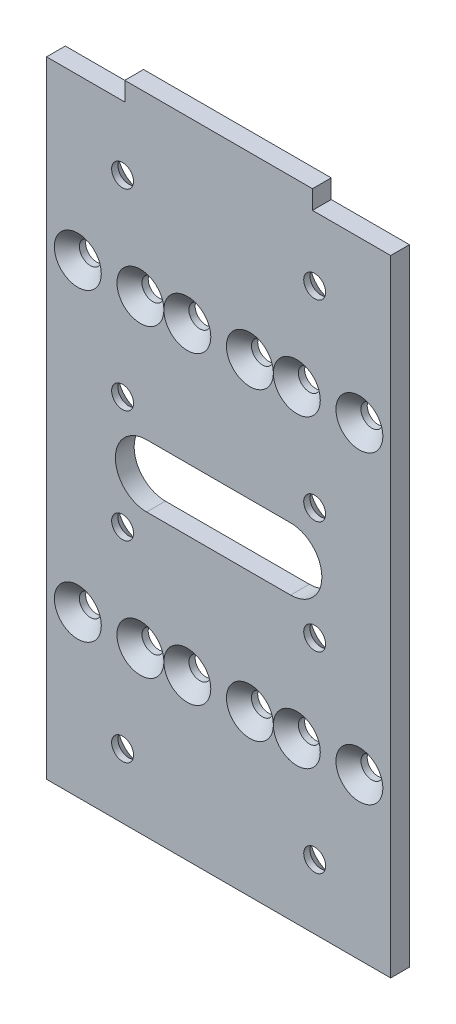
SolidWorks part; units mm, degrees
material "ABS"
ref_plane "Спереди" through (0, 0, 0) normal (0, 0, 1) x (1, 0, 0)
ref_plane "Сверху" through (0, 0, 0) normal (0, 1, 0) x (1, 0, 0)
ref_plane "Справа" through (0, 0, 0) normal (1, 0, 0) x (0, 0, -1)
sketch "Эскиз1" plane through (0, 0, 0) normal (0, 0, 1) x (1, 0, 0)
  line L1 (-27.5, -50) -> (27.5, -50)
  line L2 (-27.5, -50) -> (-27.5, 50)
  line L3 (-27.5, 50) -> (27.5, 50)
  line L4 (27.5, -50) -> (27.5, 50)
  line L5 (-27.5, -50) -> (27.5, 50) construction
  line L6 (-27.5, 50) -> (27.5, -50) construction
  line L7 (-15, 47) -> (15, 47)
  line L8 (-15, 47) -> (-15, 53)
  line L9 (-15, 53) -> (15, 53)
  line L10 (15, 47) -> (15, 53)
  line L11 (-15, 47) -> (15, 53) construction
  line L12 (-15, 53) -> (15, 47) construction
  point P0 (0, 0)
  point P6 (0, 50)
  dimension "D1" = 3
  dimension "D2" = 30
  dimension "D3" = 12.5
  dimension "D4" = 100
extrude "Бобышка-Вытянуть1" add sketch "Эскиз1" along normal blind 3 contours L10 L7 L8 L3 L2 L1 L4 | L7 L10 L3 L8 | L3 L10 L9 L8 region at (0, -0.8068, 0) region at (0, 51.5, 0) region at (0, 48.5, 0)
sketch "Эскиз2" plane through (0, 0, 3) normal (0, 0, 1) x (1, 0, 0)
  line L0 (0, 53) -> (0, -50) construction
  line L1 (-15, 53) -> (15, 53) construction
  line L2 (-27.5, -50) -> (27.5, -50) construction
  line L3 (-27.5, 0) -> (27.5, 0) construction
  line L4 (-27.5, -50) -> (-27.5, 50) construction
  line L5 (27.5, -50) -> (27.5, 50) construction
  line L6 (-15.35, -9) -> (15.35, -39.7) construction
  line L7 (-15.35, 39.7) -> (15.35, 39.7) construction
  line L8 (-15.35, 39.7) -> (-15.35, 9) construction
  line L9 (-15.35, 9) -> (15.35, 9) construction
  line L10 (15.35, 39.7) -> (15.35, 9) construction
  line L11 (-15.35, 39.7) -> (15.35, 9) construction
  line L12 (-15.35, 9) -> (15.35, 39.7) construction
  line L13 (-15.35, -39.7) -> (15.35, -9) construction
  line L14 (15.35, -39.7) -> (15.35, -9) construction
  line L15 (-15.35, -9) -> (15.35, -9) construction
  line L16 (-15.35, -39.7) -> (-15.35, -9) construction
  line L17 (-15.35, -39.7) -> (15.35, -39.7) construction
  circle A0 centre (-15.35, 39.7) radius 1.75
  circle A1 centre (15.35, 39.7) radius 1.75
  circle A2 centre (15.35, 9) radius 1.75
  circle A3 centre (-15.35, 9) radius 1.75
  circle A4 centre (-15.35, -9) radius 1.75
  circle A5 centre (15.35, -9) radius 1.75
  circle A6 centre (15.35, -39.7) radius 1.75
  circle A7 centre (-15.35, -39.7) radius 1.75
  point P12 (0, 24.35)
  point P29 (0, -24.35)
  dimension "D3" = 3.5
  dimension "D1" = 30.7
  dimension "D2" = 30.7
  dimension "D4" = 9
extrude "Вырез-Вытянуть1" cut sketch "Эскиз2" against normal blind 10
sketch "Эскиз3" plane through (0, 0, 0) normal (0, 0, -1) x (-1, 0, 0)
  line L0 (-15.35, 9) -> (15.35, 39.7) construction
  line L1 (-27.5, 24.35) -> (27.5, 24.35) construction
  line L2 (-27.5, -50) -> (-27.5, 50) construction
  line L3 (27.5, -50) -> (27.5, 50) construction
  line L4 (-27.5, 0) -> (27.5, 0) construction
  line L5 (-27.5, -24.35) -> (27.5, -24.35) construction
  line L6 (-15.35, -9) -> (15.35, -39.7) construction
  circle A0 centre (-22.5, 24.35) radius 1.75
  circle A1 centre (-12.5, 24.35) radius 1.75
  circle A2 centre (-5, 24.35) radius 1.75
  circle A3 centre (5, 24.35) radius 1.75
  circle A4 centre (12.5, 24.35) radius 1.75
  circle A5 centre (22.5, 24.35) radius 1.75
  circle A6 centre (22.5, -24.35) radius 1.75
  circle A7 centre (12.5, -24.35) radius 1.75
  circle A8 centre (5, -24.35) radius 1.75
  circle A9 centre (-5, -24.35) radius 1.75
  circle A10 centre (-12.5, -24.35) radius 1.75
  circle A11 centre (-22.5, -24.35) radius 1.75
  point P10 (0, 24.35)
  dimension "D1" = 3.5
  dimension "D2" = 3.5
  dimension "D3" = 10
  dimension "D5" = 5
  dimension "D6" = 7.5
  dimension "D4" = 3
extrude "Вырез-Вытянуть2" cut sketch "Эскиз3" against normal blind 10
chamfer "Фаска1" distance 2 angle 45 8 edges at (-13.6, 39.7, 0) (-13.6, 9, 0) (17.1, 39.7, 0) (17.1, 9, 0) (-13.6, -39.7, 0) (17.1, -39.7, 0) (-13.6, -9, 0) (17.1, -9, 0)
chamfer "Фаска2" distance 2 angle 45 12 edges at (24.25, 24.35, 3) (14.25, 24.35, 3) (6.75, 24.35, 3) (-3.25, 24.35, 3) (-10.75, 24.35, 3) (-20.75, 24.35, 3) (24.25, -24.35, 3) (14.25, -24.35, 3) (6.75, -24.35, 3) (-3.25, -24.35, 3) (-10.75, -24.35, 3) (-20.75, -24.35, 3)
sketch "Эскиз4" plane through (0, 0, 0) normal (0, 0, -1) x (-1, 0, 0)
  line L0 (-11.5, 0) -> (11.5, 0) construction
  line L1 (-11.5, 5) -> (11.5, 5)
  line L2 (-11.5, -5) -> (11.5, -5)
  arc A0 (-11.5, 5) -> (-11.5, -5) centre (-11.5, 0) ccw
  arc A1 (11.5, -5) -> (11.5, 5) centre (11.5, 0) ccw
  point P2 (0, 0)
  dimension "D1" = 10
  dimension "D2" = 23
extrude "Вырез-Вытянуть3" cut sketch "Эскиз4" against normal blind 3
